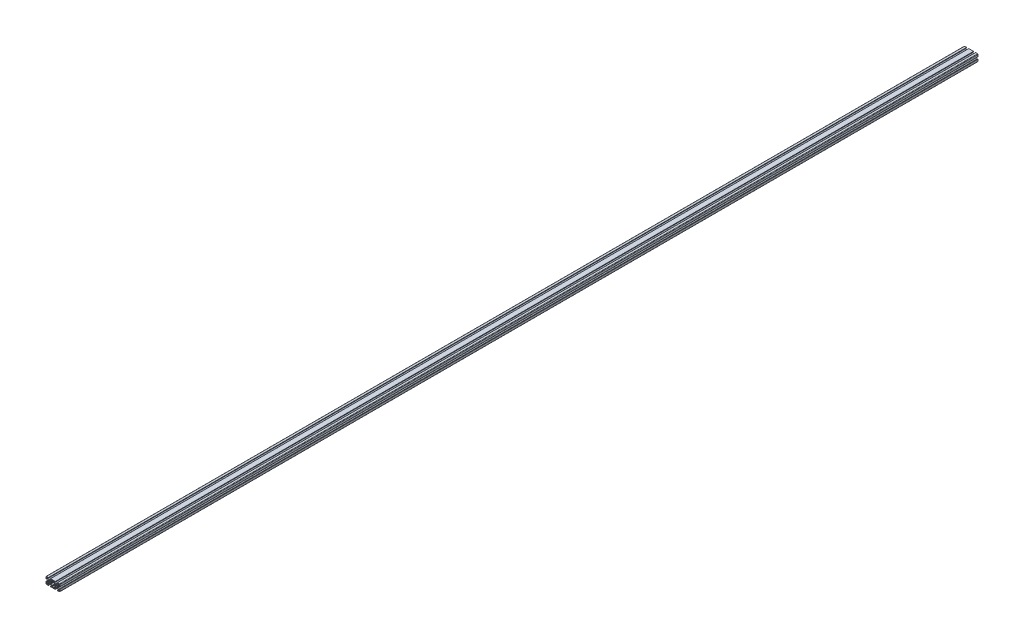
SolidWorks part; units mm, degrees
material "6105-T5 Aluminum"
ref_plane "Front Plane" through (0, 0, 0) normal (0, 0, 1) x (1, 0, 0)
ref_plane "Top Plane" through (0, 0, 0) normal (0, 1, 0) x (1, 0, 0)
ref_plane "Right Plane" through (0, 0, 0) normal (1, 0, 0) x (0, 0, -1)
sketch "Sketch1" plane through (0, 0, 0) normal (0, 0, 1) x (1, 0, 0)
  line L0 (12.7825, 3.7261) -> (13.5257, 2.983)
  line L1 (16.4743, 2.983) -> (17.2175, 3.7261)
  line L2 (18.7261, 2.2175) -> (17.983, 1.4743)
  line L3 (17.983, -1.4743) -> (18.7261, -2.2175)
  line L4 (17.2175, -3.7261) -> (16.4743, -2.983)
  line L5 (13.5257, -2.983) -> (12.7825, -3.7261)
  line L6 (11.2739, -2.2175) -> (12.017, -1.4743)
  line L7 (12.017, 1.4743) -> (11.2739, 2.2175)
  line L8 (-28.7046, 9.8946) -> (-28.7046, 12.6886)
  line L9 (-27.6886, 13.7046) -> (-24.8946, 13.7046)
  line L10 (-24.5136, 13.3236) -> (-24.5136, 9.8946)
  line L11 (-24.8946, 9.5136) -> (-28.3236, 9.5136)
  line L12 (-24.8946, -13.7046) -> (-27.6886, -13.7046)
  line L13 (-28.7046, -12.6886) -> (-28.7046, -9.8946)
  line L14 (-28.3236, -9.5136) -> (-24.8946, -9.5136)
  line L15 (-24.5136, -9.8946) -> (-24.5136, -13.3236)
  line L16 (4.9816, 8.2224) -> (9.0292, 4.1748)
  line L17 (9.178, 3.8155) -> (9.178, 0.9525)
  line L18 (9.178, 0.9525) -> (9.686, 0)
  line L19 (9.686, 0) -> (9.178, -0.9525)
  line L20 (9.178, -0.9525) -> (9.178, -3.8155)
  line L21 (9.0292, -4.1748) -> (4.9816, -8.2224)
  line L22 (4.5352, -9.3) -> (4.5352, -12.4092)
  line L23 (4.1542, -12.7902) -> (-4.1542, -12.7902)
  line L24 (-4.5352, -12.4092) -> (-4.5352, -9.3)
  line L25 (-4.9816, -8.2224) -> (-9.0292, -4.1748)
  line L26 (-9.178, -3.8155) -> (-9.178, -0.9525)
  line L27 (-9.178, -0.9525) -> (-9.686, 0)
  line L28 (-9.686, 0) -> (-9.178, 0.9525)
  line L29 (-9.178, 0.9525) -> (-9.178, 3.8155)
  line L30 (-9.0292, 4.1748) -> (-4.9816, 8.2224)
  line L31 (-4.5352, 9.3) -> (-4.5352, 12.4092)
  line L32 (-4.1542, 12.7902) -> (4.1542, 12.7902)
  line L33 (4.5352, 12.4092) -> (4.5352, 9.3)
  line L34 (-18.7261, -2.2175) -> (-17.983, -1.4743)
  line L35 (-17.983, 1.4743) -> (-18.7261, 2.2175)
  line L36 (-17.2175, 3.7261) -> (-16.4743, 2.983)
  line L37 (-13.5257, 2.983) -> (-12.7825, 3.7261)
  line L38 (-11.2739, 2.2175) -> (-12.017, 1.4743)
  line L39 (-12.017, -1.4743) -> (-11.2739, -2.2175)
  line L40 (-12.7825, -3.7261) -> (-13.5257, -2.983)
  line L41 (-16.4743, -2.983) -> (-17.2175, -3.7261)
  line L42 (24.8946, 13.7046) -> (27.6886, 13.7046)
  line L43 (28.7046, 12.6886) -> (28.7046, 9.8946)
  line L44 (28.3236, 9.5136) -> (24.8946, 9.5136)
  line L45 (24.5136, 9.8946) -> (24.5136, 13.3236)
  line L46 (24.5136, -13.3236) -> (24.5136, -9.8946)
  line L47 (24.8946, -9.5136) -> (28.3236, -9.5136)
  line L48 (28.7046, -9.8946) -> (28.7046, -12.6886)
  line L49 (27.6886, -13.7046) -> (24.8946, -13.7046)
  line L50 (-10.428, -15) -> (10.428, -15)
  line L51 (10.936, -14.492) -> (10.936, -13.2982)
  line L52 (10.428, -12.7902) -> (7.253, -12.7902)
  line L53 (6.745, -12.2822) -> (6.745, -10.2615)
  line L54 (6.8938, -9.9023) -> (10.8252, -5.9708)
  line L55 (11.1845, -5.822) -> (14.0475, -5.822)
  line L56 (14.0475, -5.822) -> (15, -5.314)
  line L57 (15, -5.314) -> (15.9525, -5.822)
  line L58 (15.9525, -5.822) -> (18.8155, -5.822)
  line L59 (19.1748, -5.9708) -> (23.1062, -9.9023)
  line L60 (23.255, -10.2615) -> (23.255, -12.2822)
  line L61 (22.747, -12.7902) -> (19.572, -12.7902)
  line L62 (19.064, -13.2982) -> (19.064, -14.492)
  line L63 (19.572, -15) -> (27.9934, -15)
  line L64 (30, -12.9934) -> (30, -4.572)
  line L65 (29.492, -4.064) -> (28.2982, -4.064)
  line L66 (27.7902, -4.572) -> (27.7902, -7.747)
  line L67 (27.2822, -8.255) -> (25.2615, -8.255)
  line L68 (24.9023, -8.1062) -> (20.9708, -4.1748)
  line L69 (20.822, -3.8155) -> (20.822, -0.9525)
  line L70 (20.822, -0.9525) -> (20.314, 0)
  line L71 (20.314, 0) -> (20.822, 0.9525)
  line L72 (20.822, 0.9525) -> (20.822, 3.8155)
  line L73 (20.9708, 4.1748) -> (24.9023, 8.1062)
  line L74 (25.2615, 8.255) -> (27.2822, 8.255)
  line L75 (27.7902, 7.747) -> (27.7902, 4.572)
  line L76 (28.2982, 4.064) -> (29.492, 4.064)
  line L77 (30, 4.572) -> (30, 12.9934)
  line L78 (27.9934, 15) -> (19.572, 15)
  line L79 (19.064, 14.492) -> (19.064, 13.2982)
  line L80 (19.572, 12.7902) -> (22.747, 12.7902)
  line L81 (23.255, 12.2822) -> (23.255, 10.2615)
  line L82 (23.1062, 9.9023) -> (19.1748, 5.9708)
  line L83 (18.8155, 5.822) -> (15.9525, 5.822)
  line L84 (15.9525, 5.822) -> (15, 5.314)
  line L85 (15, 5.314) -> (14.0475, 5.822)
  line L86 (14.0475, 5.822) -> (11.1845, 5.822)
  line L87 (10.8252, 5.9708) -> (6.8938, 9.9023)
  line L88 (6.745, 10.2615) -> (6.745, 12.2822)
  line L89 (7.253, 12.7902) -> (10.428, 12.7902)
  line L90 (10.936, 13.2982) -> (10.936, 14.492)
  line L91 (10.428, 15) -> (-10.428, 15)
  line L92 (-10.936, 14.492) -> (-10.936, 13.2982)
  line L93 (-10.428, 12.7902) -> (-7.253, 12.7902)
  line L94 (-6.745, 12.2822) -> (-6.745, 10.2615)
  line L95 (-6.8938, 9.9023) -> (-10.8252, 5.9708)
  line L96 (-11.1845, 5.822) -> (-14.0475, 5.822)
  line L97 (-14.0475, 5.822) -> (-15, 5.314)
  line L98 (-15, 5.314) -> (-15.9525, 5.822)
  line L99 (-15.9525, 5.822) -> (-18.8155, 5.822)
  line L100 (-19.1748, 5.9708) -> (-23.1062, 9.9023)
  line L101 (-23.255, 10.2615) -> (-23.255, 12.2822)
  line L102 (-22.747, 12.7902) -> (-19.572, 12.7902)
  line L103 (-19.064, 13.2982) -> (-19.064, 14.492)
  line L104 (-19.572, 15) -> (-27.9934, 15)
  line L105 (-30, 12.9934) -> (-30, 4.572)
  line L106 (-29.492, 4.064) -> (-28.2982, 4.064)
  line L107 (-27.7902, 4.572) -> (-27.7902, 7.747)
  line L108 (-27.2822, 8.255) -> (-25.2615, 8.255)
  line L109 (-24.9023, 8.1062) -> (-20.9708, 4.1748)
  line L110 (-20.822, 3.8155) -> (-20.822, 0.9525)
  line L111 (-20.822, 0.9525) -> (-20.314, 0)
  line L112 (-20.314, 0) -> (-20.822, -0.9525)
  line L113 (-20.822, -0.9525) -> (-20.822, -3.8155)
  line L114 (-20.9708, -4.1748) -> (-24.9023, -8.1062)
  line L115 (-25.2615, -8.255) -> (-27.2822, -8.255)
  line L116 (-27.7902, -7.747) -> (-27.7902, -4.572)
  line L117 (-28.2982, -4.064) -> (-29.492, -4.064)
  line L118 (-30, -4.572) -> (-30, -12.9934)
  line L119 (-27.9934, -15) -> (-19.572, -15)
  line L120 (-19.064, -14.492) -> (-19.064, -13.2982)
  line L121 (-19.572, -12.7902) -> (-22.747, -12.7902)
  line L122 (-23.255, -12.2822) -> (-23.255, -10.2615)
  line L123 (-23.1062, -9.9023) -> (-19.1748, -5.9708)
  line L124 (-18.8155, -5.822) -> (-15.9525, -5.822)
  line L125 (-15.9525, -5.822) -> (-15, -5.314)
  line L126 (-15, -5.314) -> (-14.0475, -5.822)
  line L127 (-14.0475, -5.822) -> (-11.1845, -5.822)
  line L128 (-10.8252, -5.9708) -> (-6.8938, -9.9023)
  line L129 (-6.745, -10.2615) -> (-6.745, -12.2822)
  line L130 (-7.253, -12.7902) -> (-10.428, -12.7902)
  line L131 (-10.936, -13.2982) -> (-10.936, -14.492)
  arc A0 (12.7825, 3.7261) -> (11.2739, 2.2175) centre (12.0282, 2.9718) ccw
  arc A1 (16.4743, 2.983) -> (13.5257, 2.983) centre (15, 0) ccw
  arc A2 (18.7261, 2.2175) -> (17.2175, 3.7261) centre (17.9718, 2.9718) ccw
  arc A3 (17.983, -1.4743) -> (17.983, 1.4743) centre (15, 0) ccw
  arc A4 (17.2175, -3.7261) -> (18.7261, -2.2175) centre (17.9718, -2.9718) ccw
  arc A5 (13.5257, -2.983) -> (16.4743, -2.983) centre (15, 0) ccw
  arc A6 (11.2739, -2.2175) -> (12.7825, -3.7261) centre (12.0282, -2.9718) ccw
  arc A7 (12.017, 1.4743) -> (12.017, -1.4743) centre (15, 0) ccw
  arc A8 (-28.7046, 9.8946) -> (-28.3236, 9.5136) centre (-28.3236, 9.8946) ccw
  arc A9 (-27.6886, 13.7046) -> (-28.7046, 12.6886) centre (-27.6886, 12.6886) ccw
  arc A10 (-24.5136, 13.3236) -> (-24.8946, 13.7046) centre (-24.8946, 13.3236) ccw
  arc A11 (-24.8946, 9.5136) -> (-24.5136, 9.8946) centre (-24.8946, 9.8946) ccw
  arc A12 (-24.8946, -13.7046) -> (-24.5136, -13.3236) centre (-24.8946, -13.3236) ccw
  arc A13 (-28.7046, -12.6886) -> (-27.6886, -13.7046) centre (-27.6886, -12.6886) ccw
  arc A14 (-28.3236, -9.5136) -> (-28.7046, -9.8946) centre (-28.3236, -9.8946) ccw
  arc A15 (-24.5136, -9.8946) -> (-24.8946, -9.5136) centre (-24.8946, -9.8946) ccw
  arc A16 (4.5352, 9.3) -> (4.9816, 8.2224) centre (6.0592, 9.3) ccw
  arc A17 (9.178, 3.8155) -> (9.0292, 4.1748) centre (8.67, 3.8155) ccw
  arc A18 (9.0292, -4.1748) -> (9.178, -3.8155) centre (8.67, -3.8155) ccw
  arc A19 (4.9816, -8.2224) -> (4.5352, -9.3) centre (6.0592, -9.3) ccw
  arc A20 (4.1542, -12.7902) -> (4.5352, -12.4092) centre (4.1542, -12.4092) ccw
  arc A21 (-4.5352, -12.4092) -> (-4.1542, -12.7902) centre (-4.1542, -12.4092) ccw
  arc A22 (-4.5352, -9.3) -> (-4.9816, -8.2224) centre (-6.0592, -9.3) ccw
  arc A23 (-9.178, -3.8155) -> (-9.0292, -4.1748) centre (-8.67, -3.8155) ccw
  arc A24 (-9.0292, 4.1748) -> (-9.178, 3.8155) centre (-8.67, 3.8155) ccw
  arc A25 (-4.9816, 8.2224) -> (-4.5352, 9.3) centre (-6.0592, 9.3) ccw
  arc A26 (-4.1542, 12.7902) -> (-4.5352, 12.4092) centre (-4.1542, 12.4092) ccw
  arc A27 (4.5352, 12.4092) -> (4.1542, 12.7902) centre (4.1542, 12.4092) ccw
  arc A28 (-18.7261, -2.2175) -> (-17.2175, -3.7261) centre (-17.9718, -2.9718) ccw
  arc A29 (-17.983, 1.4743) -> (-17.983, -1.4743) centre (-15, 0) ccw
  arc A30 (-17.2175, 3.7261) -> (-18.7261, 2.2175) centre (-17.9718, 2.9718) ccw
  arc A31 (-13.5257, 2.983) -> (-16.4743, 2.983) centre (-15, 0) ccw
  arc A32 (-11.2739, 2.2175) -> (-12.7825, 3.7261) centre (-12.0282, 2.9718) ccw
  arc A33 (-12.017, -1.4743) -> (-12.017, 1.4743) centre (-15, 0) ccw
  arc A34 (-12.7825, -3.7261) -> (-11.2739, -2.2175) centre (-12.0282, -2.9718) ccw
  arc A35 (-16.4743, -2.983) -> (-13.5257, -2.983) centre (-15, 0) ccw
  arc A36 (24.8946, 13.7046) -> (24.5136, 13.3236) centre (24.8946, 13.3236) ccw
  arc A37 (28.7046, 12.6886) -> (27.6886, 13.7046) centre (27.6886, 12.6886) ccw
  arc A38 (28.3236, 9.5136) -> (28.7046, 9.8946) centre (28.3236, 9.8946) ccw
  arc A39 (24.5136, 9.8946) -> (24.8946, 9.5136) centre (24.8946, 9.8946) ccw
  arc A40 (24.5136, -13.3236) -> (24.8946, -13.7046) centre (24.8946, -13.3236) ccw
  arc A41 (24.8946, -9.5136) -> (24.5136, -9.8946) centre (24.8946, -9.8946) ccw
  arc A42 (28.7046, -9.8946) -> (28.3236, -9.5136) centre (28.3236, -9.8946) ccw
  arc A43 (27.6886, -13.7046) -> (28.7046, -12.6886) centre (27.6886, -12.6886) ccw
  arc A44 (10.428, -15) -> (10.936, -14.492) centre (10.428, -14.492) ccw
  arc A45 (10.936, -13.2982) -> (10.428, -12.7902) centre (10.428, -13.2982) ccw
  arc A46 (6.745, -12.2822) -> (7.253, -12.7902) centre (7.253, -12.2822) ccw
  arc A47 (6.8938, -9.9023) -> (6.745, -10.2615) centre (7.253, -10.2615) ccw
  arc A48 (11.1845, -5.822) -> (10.8252, -5.9708) centre (11.1845, -6.33) ccw
  arc A49 (19.1748, -5.9708) -> (18.8155, -5.822) centre (18.8155, -6.33) ccw
  arc A50 (23.255, -10.2615) -> (23.1062, -9.9023) centre (22.747, -10.2615) ccw
  arc A51 (22.747, -12.7902) -> (23.255, -12.2822) centre (22.747, -12.2822) ccw
  arc A52 (19.572, -12.7902) -> (19.064, -13.2982) centre (19.572, -13.2982) ccw
  arc A53 (19.064, -14.492) -> (19.572, -15) centre (19.572, -14.492) ccw
  arc A54 (27.9934, -15) -> (30, -12.9934) centre (27.9934, -12.9934) ccw
  arc A55 (30, -4.572) -> (29.492, -4.064) centre (29.492, -4.572) ccw
  arc A56 (28.2982, -4.064) -> (27.7902, -4.572) centre (28.2982, -4.572) ccw
  arc A57 (27.2822, -8.255) -> (27.7902, -7.747) centre (27.2822, -7.747) ccw
  arc A58 (24.9023, -8.1062) -> (25.2615, -8.255) centre (25.2615, -7.747) ccw
  arc A59 (20.822, -3.8155) -> (20.9708, -4.1748) centre (21.33, -3.8155) ccw
  arc A60 (20.9708, 4.1748) -> (20.822, 3.8155) centre (21.33, 3.8155) ccw
  arc A61 (25.2615, 8.255) -> (24.9023, 8.1062) centre (25.2615, 7.747) ccw
  arc A62 (27.7902, 7.747) -> (27.2822, 8.255) centre (27.2822, 7.747) ccw
  arc A63 (27.7902, 4.572) -> (28.2982, 4.064) centre (28.2982, 4.572) ccw
  arc A64 (29.492, 4.064) -> (30, 4.572) centre (29.492, 4.572) ccw
  arc A65 (30, 12.9934) -> (27.9934, 15) centre (27.9934, 12.9934) ccw
  arc A66 (19.572, 15) -> (19.064, 14.492) centre (19.572, 14.492) ccw
  arc A67 (19.064, 13.2982) -> (19.572, 12.7902) centre (19.572, 13.2982) ccw
  arc A68 (23.255, 12.2822) -> (22.747, 12.7902) centre (22.747, 12.2822) ccw
  arc A69 (23.1062, 9.9023) -> (23.255, 10.2615) centre (22.747, 10.2615) ccw
  arc A70 (18.8155, 5.822) -> (19.1748, 5.9708) centre (18.8155, 6.33) ccw
  arc A71 (10.8252, 5.9708) -> (11.1845, 5.822) centre (11.1845, 6.33) ccw
  arc A72 (6.745, 10.2615) -> (6.8938, 9.9023) centre (7.253, 10.2615) ccw
  arc A73 (7.253, 12.7902) -> (6.745, 12.2822) centre (7.253, 12.2822) ccw
  arc A74 (10.428, 12.7902) -> (10.936, 13.2982) centre (10.428, 13.2982) ccw
  arc A75 (10.936, 14.492) -> (10.428, 15) centre (10.428, 14.492) ccw
  arc A76 (-10.428, 15) -> (-10.936, 14.492) centre (-10.428, 14.492) ccw
  arc A77 (-10.936, 13.2982) -> (-10.428, 12.7902) centre (-10.428, 13.2982) ccw
  arc A78 (-6.745, 12.2822) -> (-7.253, 12.7902) centre (-7.253, 12.2822) ccw
  arc A79 (-6.8938, 9.9023) -> (-6.745, 10.2615) centre (-7.253, 10.2615) ccw
  arc A80 (-11.1845, 5.822) -> (-10.8252, 5.9708) centre (-11.1845, 6.33) ccw
  arc A81 (-19.1748, 5.9708) -> (-18.8155, 5.822) centre (-18.8155, 6.33) ccw
  arc A82 (-23.255, 10.2615) -> (-23.1062, 9.9023) centre (-22.747, 10.2615) ccw
  arc A83 (-22.747, 12.7902) -> (-23.255, 12.2822) centre (-22.747, 12.2822) ccw
  arc A84 (-19.572, 12.7902) -> (-19.064, 13.2982) centre (-19.572, 13.2982) ccw
  arc A85 (-19.064, 14.492) -> (-19.572, 15) centre (-19.572, 14.492) ccw
  arc A86 (-27.9934, 15) -> (-30, 12.9934) centre (-27.9934, 12.9934) ccw
  arc A87 (-30, 4.572) -> (-29.492, 4.064) centre (-29.492, 4.572) ccw
  arc A88 (-28.2982, 4.064) -> (-27.7902, 4.572) centre (-28.2982, 4.572) ccw
  arc A89 (-27.2822, 8.255) -> (-27.7902, 7.747) centre (-27.2822, 7.747) ccw
  arc A90 (-24.9023, 8.1062) -> (-25.2615, 8.255) centre (-25.2615, 7.747) ccw
  arc A91 (-20.822, 3.8155) -> (-20.9708, 4.1748) centre (-21.33, 3.8155) ccw
  arc A92 (-20.9708, -4.1748) -> (-20.822, -3.8155) centre (-21.33, -3.8155) ccw
  arc A93 (-25.2615, -8.255) -> (-24.9023, -8.1062) centre (-25.2615, -7.747) ccw
  arc A94 (-27.7902, -7.747) -> (-27.2822, -8.255) centre (-27.2822, -7.747) ccw
  arc A95 (-27.7902, -4.572) -> (-28.2982, -4.064) centre (-28.2982, -4.572) ccw
  arc A96 (-29.492, -4.064) -> (-30, -4.572) centre (-29.492, -4.572) ccw
  arc A97 (-30, -12.9934) -> (-27.9934, -15) centre (-27.9934, -12.9934) ccw
  arc A98 (-19.572, -15) -> (-19.064, -14.492) centre (-19.572, -14.492) ccw
  arc A99 (-19.064, -13.2982) -> (-19.572, -12.7902) centre (-19.572, -13.2982) ccw
  arc A100 (-23.255, -12.2822) -> (-22.747, -12.7902) centre (-22.747, -12.2822) ccw
  arc A101 (-23.1062, -9.9023) -> (-23.255, -10.2615) centre (-22.747, -10.2615) ccw
  arc A102 (-18.8155, -5.822) -> (-19.1748, -5.9708) centre (-18.8155, -6.33) ccw
  arc A103 (-10.8252, -5.9708) -> (-11.1845, -5.822) centre (-11.1845, -6.33) ccw
  arc A104 (-6.745, -10.2615) -> (-6.8938, -9.9023) centre (-7.253, -10.2615) ccw
  arc A105 (-7.253, -12.7902) -> (-6.745, -12.2822) centre (-7.253, -12.2822) ccw
  arc A106 (-10.428, -12.7902) -> (-10.936, -13.2982) centre (-10.428, -13.2982) ccw
  arc A107 (-10.936, -14.492) -> (-10.428, -15) centre (-10.428, -14.492) ccw
extrude "Extrude1" add sketch "Sketch1" against normal blind 4000
